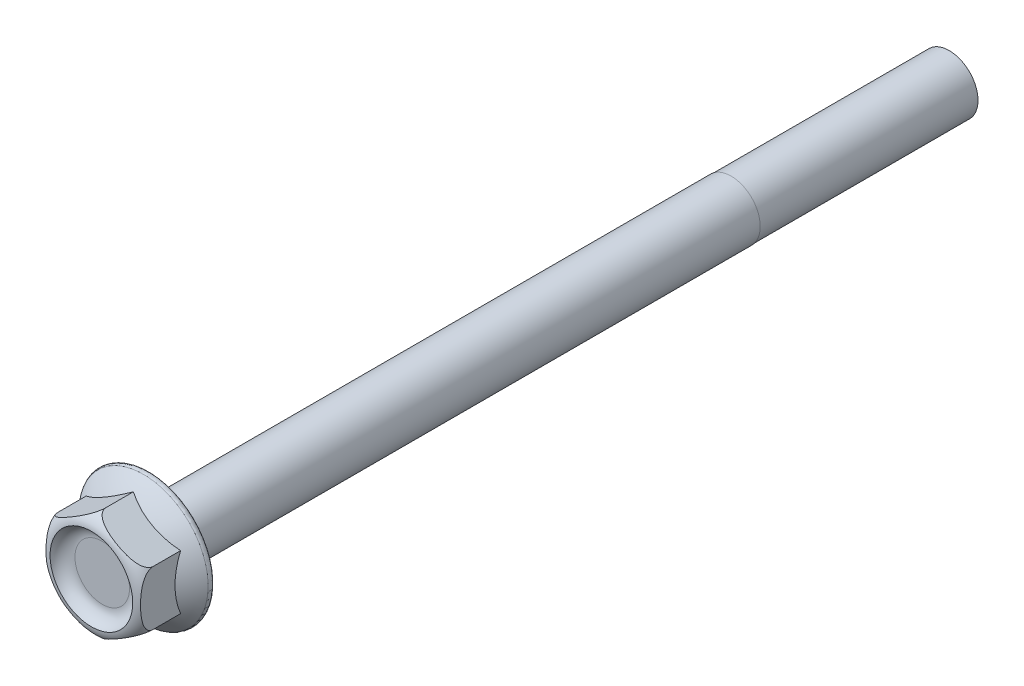
SolidWorks part; units mm, degrees
note: '?' marks a value the reader was unsure of.
extrude "Shank" add sketch "Shank Sketch" against normal blind 110
sketch "Shank Sketch" plane through (0, 0, 0) normal (0, 0, 1) x (1, 0, 0)
  line L0 (50, 0) -> (-50, 0) construction
  line L1 (0, -50) -> (0, 50) construction
  circle A0 centre (0, 0) radius 4
  dimension "Shank diameter" = 8
extrude "Head" add sketch "Head Sketch" along normal blind 8
sketch "Head Sketch" plane through (0, 0, 0) normal (0, 0, 1) x (1, 0, 0)
  line L0 (0, 7.5056) -> (6.5, 3.7528)
  line L1 (6.5, 3.7528) -> (6.5, -3.7528)
  line L2 (6.5, -3.7528) -> (0, -7.5056)
  line L3 (0, -7.5056) -> (-6.5, -3.7528)
  line L4 (-6.5, -3.7528) -> (-6.5, 3.7528)
  line L5 (-6.5, 3.7528) -> (0, 7.5056)
  line L6 (6.5, 3.7528) -> (-6.5, -3.7528) construction
  line L7 (0, 7.5056) -> (0, -7.5056) construction
  line L8 (-6.5, 3.7528) -> (6.5, -3.7528) construction
  point P0 (0, 0)
  dimension "D1" = 60
  dimension "D2" = 60
  dimension "Width across flats" = 13
ref_plane "Plane1" through (0, 0, 0) normal (0, 0, 1) x (1, 0, 0)
ref_plane "Plane2" through (0, 0, 0) normal (0, 1, 0) x (-1, 0, 0)
ref_plane "Plane3" through (0, 0, 0) normal (1, 0, 0) x (0, 0, -1)
other "Configuration Table"
sketch "Sketch3" plane through (0, 0, 0) normal (0, 1, 0) x (-1, 0, 0)
  line L0 (0, 0) -> (0, 10) construction
  line L1 (0, -110) -> (0, 0) construction
  line L4 (-8.5, 0) -> (0, 0)
  line L5 (0, 0) -> (0, 5)
  arc A0 (0, 5) -> (-8.8853, 0.8187) centre (0, -6.5313) ccw
  arc A1 (-8.5, 0) -> (-8.8853, 0.8187) centre (-8.5, 0.5) cw
  dimension "D1" = 0.5
  dimension "D2" = 17
  dimension "D3" = 5
revolve "Flange" add sketch "Sketch3" angle 360 about L0
ref_axis "Axis1" through (0, 0, -160) along (0, 0, 1)?
sketch "Sketch5" plane through (0, 0, 0) normal (1, 0, 0) x (0, 0, -1)
  line L0 (-8, -5.5056) -> (-8, -7.5056)
  line L1 (-8, -7.5056) -> (-6, -7.5056)
  line L2 (-8, -7.5056) -> (-2.223, -7.5056) construction
  line L3 (-8, -7.5056) -> (-8, -3.7528) construction
  line L5 (-15.0856, 0) -> (-8.1394, 0) construction
  line L6 (50, 0) -> (-50, 0) construction
  arc A0 (-8, -5.5056) -> (-6, -7.5056) centre (-6, -5.5056) ccw
  dimension "D1" = 2
revolve "Head Trim" cut sketch "Sketch5" angle 360 about L5
sketch "Sketch6" plane through (0, 0, 8) normal (0, 0, 1) x (1, 0, 0)
  circle A3 centre (0, 0) radius 5.6875
extrude "Head Cut" cut sketch "Sketch6" against normal blind 1.5
fillet "Fillet1" radius 2 1 edges at (5.6875, 0, 6.5)
fillet "Fillet2" radius 0.5 1 edges at (4, 0, 0)
sketch "Thread End" plane through (0, 0, 0) normal (1, 0, 0) x (0, 0, -1)
  line L0 (80, 4) -> (80, 3.95)
  line L1 (110, 4) -> (0.5, 4) construction
  line L2 (80, 3.95) -> (110, 3.95)
  line L3 (110, 4) -> (80, 4)
  line L4 (21.5519, 0) -> (27.4271, 0) construction
  line L5 (110, 0) -> (0.5, 0) construction
  line L6 (110, -4) -> (110, 4) construction
  line L7 (110, 3.95) -> (110, 4)
  dimension "D1" = 0.05
  dimension "Length of thread" = 30
revolve "Thread Cut" cut sketch "Thread End" angle 360 about L4
cosmetic thread "Cosmetic Thread2" parameters "D2"=11
equation "\"D1@Sketch6\" = \"Width across flats@Head Sketch\"*7/8"
